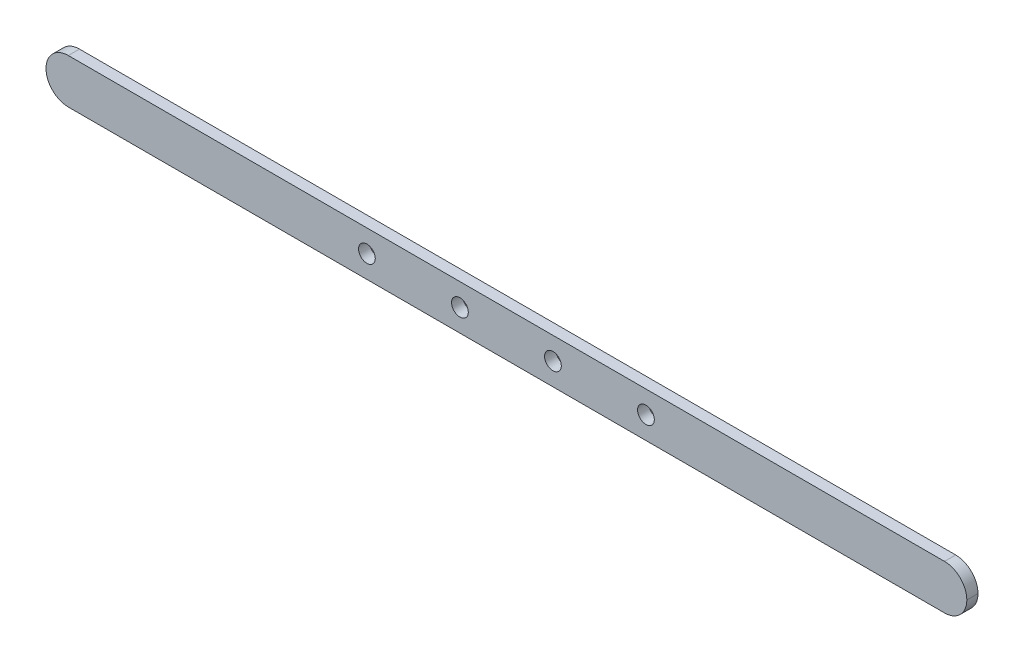
SolidWorks part; units mm, degrees
ref_plane "Front Plane" through (0, 0, 0) normal (0, 0, 1) x (1, 0, 0)
ref_plane "Top Plane" through (0, 0, 0) normal (0, 1, 0) x (1, 0, 0)
ref_plane "Right Plane" through (0, 0, 0) normal (1, 0, 0) x (0, 0, -1)
sketch "Sketch1" plane through (0, 0, 0) normal (0, 0, 1) x (1, 0, 0)
  line L0 (0, 0) -> (75, 0)
  line L1 (-247.5, -12) -> (247.5, -12)
  line L2 (-247.5, -12) -> (-247.5, 12)
  line L3 (-247.5, 12) -> (247.5, 12)
  line L4 (247.5, -12) -> (247.5, 12)
  line L5 (-247.5, -12) -> (247.5, 12) construction
  line L6 (-247.5, 12) -> (247.5, -12) construction
  circle A0 centre (75, 0) radius 4.5
  circle A1 centre (25, 0) radius 4.5
  circle A2 centre (-25, 0) radius 4.5
  circle A3 centre (-75, 0) radius 4.5
  point P0 (0, 0)
  dimension "D4" = 9
  dimension "D1" = 24
  dimension "D2" = 495
  dimension "D3" = 75
  dimension "D6" = 25
  dimension "D5" = 4
extrude "Boss-Extrude1" add sketch "Sketch1" along normal blind 6 contours L1 L4 L3 L2 A3 A2 A1 A0 region at (-242.5442, 0, 0)
fillet "Fillet2" radius 12 4 edges at (-247.5, -12, 3) (-247.5, 12, 3) (247.5, 12, 3) (247.5, -12, 3)
